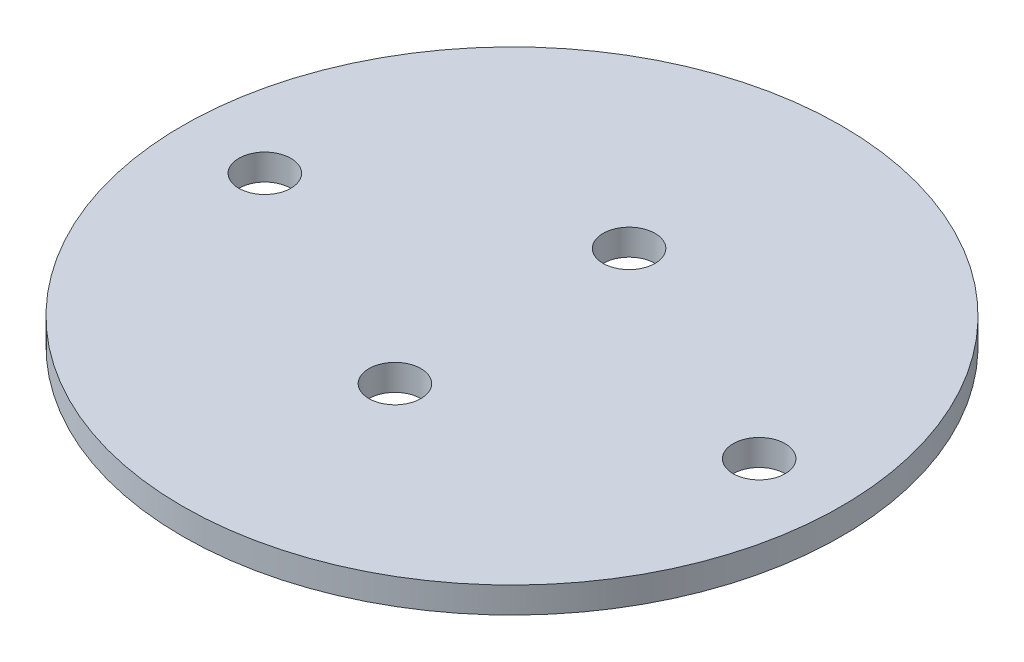
SolidWorks part; units mm, degrees
ref_plane "Front Plane" through (0, 0, 0) normal (0, 0, 1) x (1, 0, 0)
ref_plane "Top Plane" through (0, 0, 0) normal (0, 1, 0) x (1, 0, 0)
ref_plane "Right Plane" through (0, 0, 0) normal (1, 0, 0) x (0, 0, -1)
sketch "Sketch1" plane through (0, 0, 0) normal (0, 1, 0) x (1, 0, 0)
  line L0 (-28.5, 0) -> (28.5, 0) construction
  line L1 (0, 0) -> (0, 13.5)
  line L2 (0, 0) -> (0, -13.5)
  circle A0 centre (0, 0) radius 38
  circle A1 centre (28.5, 0) radius 3
  circle A2 centre (-28.5, 0) radius 3
  circle A3 centre (0, 13.5) radius 3
  circle A4 centre (0, -13.5) radius 3
  circle A5 centre (-28.5, 0) radius 6.25 construction
  circle A6 centre (0, 13.5) radius 12.5 construction
  circle A7 centre (0, -13.5) radius 12.5 construction
  circle A8 centre (28.5, 0) radius 6.25 construction
  point P2 (8.657, 15.1829)
  point P11 (0, 0)
  dimension "D1" = 76
  dimension "D3" = 6
  dimension "D4" = 13.5
  dimension "D5" = 6
  dimension "D6" = 12.5
  dimension "D7" = 25
  dimension "D2" = 57
extrude "Boss-Extrude1" add sketch "Sketch1" against normal blind 3 contours A0 A4 A3 A2 A1 region at (-36.9252, 0, 0)
